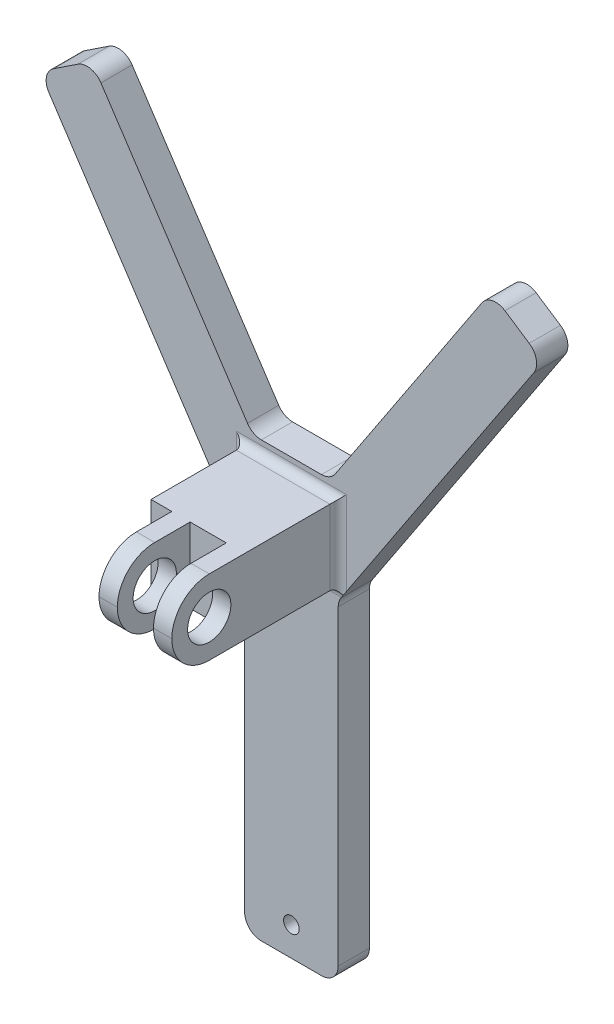
SolidWorks part; units mm, degrees
ref_plane "Plan de face" through (0, 0, 0) normal (0, 0, 1) x (1, 0, 0)
ref_plane "Plan de dessus" through (0, 0, 0) normal (0, 1, 0) x (1, 0, 0)
ref_plane "Plan de droite" through (0, 0, 0) normal (1, 0, 0) x (0, 0, -1)
sketch "Sketch1" plane through (0, 0, 0) normal (0, 0, 1) x (1, 0, 0)
  line L18 (-11.895, 65.5892) -> (11.895, 65.5892)
  line L19 (11.895, 65.5892) -> (60.9587, 139.724)
  line L20 (60.9587, 139.724) -> (76.8447, 129.2103)
  line L21 (76.8447, 129.2103) -> (14.2875, 34.687)
  line L23 (14.2875, 34.687) -> (14.2875, -66.913)
  line L24 (14.2875, -66.913) -> (-14.2875, -66.913)
  line L25 (-14.2875, -66.913) -> (-14.2875, 34.687)
  line L26 (-14.2875, 34.687) -> (-76.8447, 129.2103)
  line L27 (-76.8447, 129.2103) -> (-60.9587, 139.724)
  line L28 (-60.9587, 139.724) -> (-11.895, 65.5892)
  line L29 (-14.2875, 34.687) -> (14.2875, 34.687) construction
  point P2 (0, 34.687)
  point P12 (0, 65.5892)
  dimension "D1" = 28.575
  dimension "D2" = 19.05
  dimension "D3" = 88.9
  dimension "D4" = 88.9
  dimension "D5" = 101.6
extrude "Boss-Extrude1" add sketch "Sketch1" along normal blind 9.525
sketch "Sketch3" plane through (0, 0, 9.525) normal (0, 0, 1) x (1, 0, 0)
  line L0 (0, 65.5892) -> (0, 34.687) construction
  line L5 (14.2875, 38.7081) -> (-14.2875, 38.7081)
  line L6 (14.2875, 38.7081) -> (14.2875, 61.5681)
  line L7 (14.2875, 61.5681) -> (-14.2875, 61.5681)
  line L8 (-14.2875, 38.7081) -> (-14.2875, 61.5681)
  line L9 (14.2875, 38.7081) -> (-14.2875, 61.5681) construction
  line L10 (14.2875, 61.5681) -> (-14.2875, 38.7081) construction
  line L12 (11.895, 65.5892) -> (-11.895, 65.5892) construction
  point P0 (0, 50.1381)
  point P15 (0, 50.1381)
  dimension "D1" = 28.575
  dimension "D2" = 22.86
extrude "Boss-Extrude2" add sketch "Sketch3" along normal blind 50.8
sketch "Sketch6" plane through (0, 0, 9.525) normal (0, 0, 1) x (1, 0, 0)
  line L6 (-14.2875, 34.687) -> (-14.2875, -66.913) construction
  line L11 (-14.2875, 38.7081) -> (14.2875, 38.7081)
  line L12 (-14.2875, 38.7081) -> (-14.2875, -66.913)
  line L13 (-14.2875, -66.913) -> (14.2875, -66.913)
  line L14 (14.2875, 38.7081) -> (14.2875, -66.913)
  line L15 (-14.2875, -66.913) -> (14.2875, -66.913) construction
  line L16 (14.2875, -66.913) -> (14.2875, 34.687) construction
  line L17 (-14.2875, 38.7081) -> (14.2875, 38.7081) construction
extrude "Boss-Extrude3" [suppressed] add sketch "Sketch6" along normal blind 5.08
fillet "Fillet1" radius 5.08 10 edges at (-14.2875, -66.913, 4.7625) (14.2875, -66.913, 4.7625) (76.8447, 129.2103, 4.7625) (60.9587, 139.724, 4.7625) (-60.9587, 139.724, 4.7625) (-76.8447, 129.2103, 4.7625) (-11.895, 65.5892, 4.7625) (11.895, 65.5892, 4.7625) (14.2875, 34.687, 4.7625) (-14.2875, 34.687, 4.7625)
sketch "Sketch4" plane through (0, 38.7081, 0) normal (0, -1, 0) x (1, 0, 0)
  line L0 (-14.2875, 60.325) -> (14.2875, 60.325) construction
  line L1 (-14.2875, 60.325) -> (-7.9375, 60.325)
  line L2 (-14.2875, 60.325) -> (-14.2875, 38.1)
  line L3 (-14.2875, 38.1) -> (-7.9375, 38.1)
  line L4 (-7.9375, 60.325) -> (-7.9375, 38.1)
  line L5 (-2.3495, 60.325) -> (8.6995, 60.325)
  line L6 (-2.3495, 60.325) -> (-2.3495, 38.1)
  line L7 (-2.3495, 38.1) -> (8.6995, 38.1)
  line L8 (8.6995, 60.325) -> (8.6995, 38.1)
  line L9 (14.2875, 60.325) -> (14.2875, 9.525) construction
  dimension "D1" = 5.588
  dimension "D2" = 5.588
  dimension "D3" = 22.225
  dimension "D4" = 22.225
  dimension "D5" = 6.35
extrude "Cut-Extrude1" cut sketch "Sketch4" against normal through all
fillet "Fillet3" radius 11.43 4 edges at (11.4935, 61.5681, 60.325) (-5.1435, 61.5681, 60.325) (11.4935, 38.7081, 60.325) (-5.1435, 38.7081, 60.325)
sketch "Sketch5" plane through (-7.9375, 0, 0) normal (-1, 0, 0) x (0, 0, 1)
  circle A0 centre (48.895, 50.1381) radius 6.604
  dimension "D1" = 13.208
extrude "Cut-Extrude2" cut sketch "Sketch5" against normal through all
fillet "Fillet6" [suppressed] radius 2.54
sketch "Sketch7" plane through (0, 0, 0) normal (0, 0, -1) x (-1, 0, 0)
  line L0 (9.2075, -66.913) -> (-9.2075, -66.913) construction
  line L1 (14.2875, 33.1582) -> (14.2875, -61.833) construction
  circle A0 centre (0, -58.023) radius 4.2333
  dimension "D1" = 8.4667
  dimension "D2" = 8.89
  dimension "D3" = 14.2875
extrude "Cut-Extrude3" cut sketch "Sketch7" against normal blind 5.08
sketch "Sketch8" plane through (0, 0, 5.08) normal (0, 0, -1) x (-1, 0, 0)
  line L0 (14.2875, 33.1582) -> (14.2875, -61.833) construction
  line L2 (9.2075, -66.913) -> (-9.2075, -66.913) construction
  circle A0 centre (0, -58.023) radius 2.3812
  dimension "D1" = 4.7625
  dimension "D2" = 14.2875
  dimension "D3" = 8.89
extrude "Cut-Extrude4" cut sketch "Sketch8" against normal through all
fillet "Fillet7" radius 2.54 4 edges at (-14.2875, 50.1381, 9.525) (0, 61.5681, 9.525) (14.2875, 50.1381, 9.525) (0, 38.7081, 9.525)
